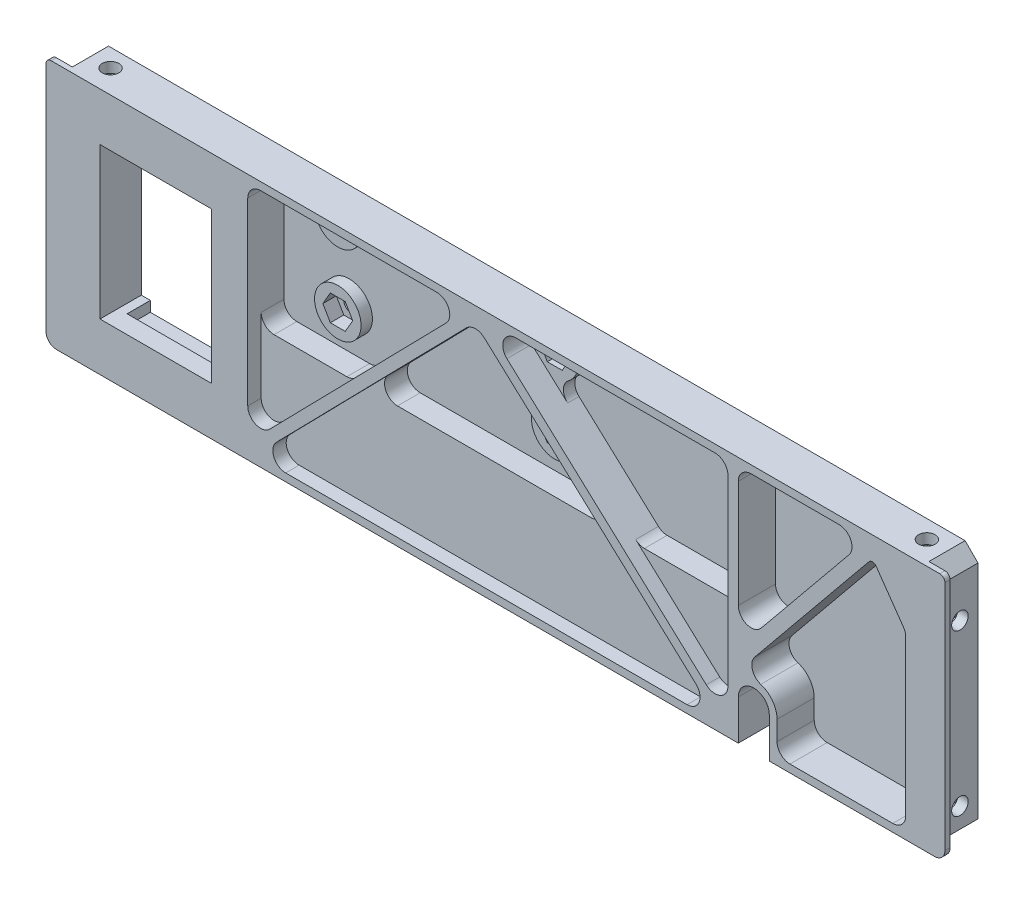
SolidWorks part; units mm, degrees
ref_plane "Front Plane" through (0, 0, 0) normal (0, 0, 1) x (1, 0, 0)
ref_plane "Top Plane" through (0, 0, 0) normal (0, 1, 0) x (1, 0, 0)
ref_plane "Right Plane" through (0, 0, 0) normal (1, 0, 0) x (0, 0, -1)
sketch "Sketch1" plane through (0, 0, 0) normal (0, 0, 1) x (1, 0, 0)
  line L1 (87, -25.55) -> (-87, -25.55)
  line L2 (87, -25.55) -> (87, 25.55)
  line L3 (87, 25.55) -> (-87, 25.55)
  line L4 (-87, -25.55) -> (-87, 25.55)
  line L5 (87, -25.55) -> (-87, 25.55) construction
  line L6 (87, 25.55) -> (-87, -25.55) construction
  point P0 (0, 0)
  dimension "D1" = 174
  dimension "D2" = 51.1
extrude "Boss-Extrude1" add sketch "Sketch1" against normal blind 8
sketch "Sketch2" plane through (0, 0, -8) normal (0, 0, -1) x (-1, 0, 0)
  line L5 (-87, -25.55) -> (-87, 25.55) construction
  line L6 (-87, 25.55) -> (87, 25.55) construction
  line L13 (85.4, -23.95) -> (85.4, 23.95)
  line L14 (-85.4, -23.95) -> (85.4, -23.95)
  line L15 (-85.4, 23.95) -> (-85.4, -23.95)
  line L16 (85.4, 23.95) -> (-85.4, 23.95)
  point P2 (0, 23.95)
  point P5 (85.4, 0)
  dimension "D1" = 1.6
  dimension "D2" = 1.6
extrude "Cut-Extrude1" cut sketch "Sketch2" against normal offset from surface (7 mm away) 1 flip side to cut up to face at (0, 0, 0)
chamfer "Chamfer1" distance 2.5 angle 45 4 edges at (-85.4, -23.95, -4.5) (-85.4, 23.95, -4.5) (85.4, -23.95, -4.5) (85.4, 23.95, -4.5)
fillet "Fillet1" radius 0.5 2 edges at (-87, 25.55, -0.5) (87, 25.55, -0.5)
sketch "Sketch3" plane through (0, 0, 0) normal (0, 0, 1) x (1, 0, 0)
  line L1 (-82.9, 23.95) -> (-85.4, 21.45) construction
  line L2 (-82.9, 23.95) -> (82.9, 23.95) construction
  line L3 (-82.9, 23.95) -> (-85.4, 21.45) construction
  line L4 (-82.9, 23.95) -> (82.9, 23.95) construction
  line L5 (85.4, 21.45) -> (82.9, 23.95) construction
  line L6 (85.4, 21.45) -> (85.4, -21.45) construction
  line L7 (82.9, -23.95) -> (85.4, -21.45) construction
  line L8 (82.9, -23.95) -> (-82.9, -23.95) construction
  line L9 (-85.4, -21.45) -> (-82.9, -23.95) construction
  line L10 (-85.4, -21.45) -> (-85.4, 21.45) construction
  line L11 (85.4, 21.45) -> (82.9, 23.95) construction
  line L12 (85.4, 21.45) -> (85.4, -21.45) construction
  line L13 (82.9, -23.95) -> (85.4, -21.45) construction
  line L14 (82.9, -23.95) -> (-82.9, -23.95) construction
  line L15 (-85.4, -21.45) -> (-82.9, -23.95) construction
  line L16 (-85.4, -21.45) -> (-85.4, 21.45) construction
  line L26 (79.4, -22.45) -> (-79.4, -22.45)
  line L27 (79.4, -22.45) -> (79.4, 22.45)
  line L28 (79.4, 22.45) -> (-79.4, 22.45)
  line L29 (-79.4, -22.45) -> (-79.4, 22.45)
  line L30 (79.4, -22.45) -> (-79.4, 22.45) construction
  line L31 (79.4, 22.45) -> (-79.4, -22.45) construction
  point P4 (0, 0)
  dimension "D1" = 3
  dimension "D2" = 6
extrude "Cut-Extrude2" cut sketch "Sketch3" against normal offset from surface (7.2 mm away) 0.8 up to face at (0, 0, -8)
sketch "Sketch9" plane through (0, 0, 0) normal (0, 0, 1) x (1, 0, 0)
  line L0 (-73.4, 22.45) -> (-73.4, 19.45)
  line L1 (-79.4, 22.45) -> (79.4, 22.45) construction
  line L2 (-73.4, 19.45) -> (-79.4, 10.8811)
  line L3 (-79.4, -22.45) -> (-79.4, 22.45) construction
  line L4 (-79.4, 10.8811) -> (-79.4, 22.45)
  line L5 (-79.4, 22.45) -> (-73.4, 22.45)
  dimension "D1" = 6
  dimension "D2" = 35
  dimension "D3" = 3
extrude "Boss-Extrude2" add sketch "Sketch9" against normal up to surface (7.2 mm away) up to face at (0, 0, -7.2)
hole_wizard "Ø3.0mm Dowel Hole1" positions "Sketch4" profile "Sketch5" hole size "Ø3.0" standard "ANSI Metric"
sketch "Sketch4" plane through (-85.4, 0, 0) normal (-1, 0, 0) x (0, 0, 1)
  line L0 (-4.5, 13.55) -> (-4.5, -17.55) construction
  line L2 (-8, -21.45) -> (-8, 21.45) construction
  line L3 (-1, 25.55) -> (0, 25.55) construction
  line L5 (-1, -25.55) -> (0, -25.55) construction
  point P0 (-4.5, 13.55)
  point P3 (-4.5, -17.55)
  point P15 (-0.5, 25.55)
  dimension "D1" = 3.5
  dimension "D2" = 12
  dimension "D3" = 8
sketch "Sketch5" plane through (-85.4, 13.55, -4.5) normal (0, 1, 0) x (0, 0, 1)
  line L0 (0, 0) -> (0, 5)
  line L1 (0, 5) -> (1.6, 5)
  line L2 (1.6, 5) -> (1.6, 0)
  line L5 (1.6, 0) -> (0, 0)
  line L10 (0, 5) -> (-1.6, 5) construction
  line L11 (0, -6.35) -> (0, 107.95) construction
  dimension "Hole Dia." = 3.2
  dimension "Hole Depth" = 5
  dimension "Drill Angle" = 180
hole_wizard "Ø3.0mm Dowel Hole2" positions "Sketch7" profile "Sketch8" hole size "Ø3.0" standard "ANSI Metric"
sketch "Sketch7" plane through (0, 23.95, 0) normal (0, 1, 0) x (1, 0, 0)
  line L0 (-82.9, 8) -> (82.9, 8) construction
  line L1 (-87, 0) -> (-87, 1) construction
  point P0 (-79, 4.5)
  dimension "D1" = 3.5
  dimension "D2" = 8
sketch "Sketch8" plane through (-79, 23.95, -4.5) normal (1, 0, 0) x (0, 0, 1)
  line L0 (0, 0) -> (0, 5)
  line L1 (0, 5) -> (1.6, 5)
  line L2 (1.6, 5) -> (1.6, 0)
  line L5 (1.6, 0) -> (0, 0)
  line L10 (0, 5) -> (-1.6, 5) construction
  line L11 (0, -6.35) -> (0, 107.95) construction
  dimension "Hole Dia." = 3.2
  dimension "Hole Depth" = 5
  dimension "Drill Angle" = 180
sketch "Sketch10" plane through (-85.4, 0, 0) normal (-1, 0, 0) x (0, 0, 1)
  line L0 (-8, -21.45) -> (-8, 21.45) construction
  line L1 (-8, 16.3) -> (-1.75, 16.3)
  line L2 (-8, 16.3) -> (-8, 10.8)
  line L3 (-8, 10.8) -> (-1.75, 10.8)
  line L4 (-1.75, 16.3) -> (-1.75, 10.8)
  line L6 (-8, -14.8) -> (-1.75, -14.8)
  line L7 (-8, -14.8) -> (-8, -20.3)
  line L8 (-8, -20.3) -> (-1.75, -20.3)
  line L9 (-1.75, -14.8) -> (-1.75, -20.3)
  point P6 (-1.75, -17.55)
  point P8 (-1.75, 13.55)
  dimension "D1" = 5.5
  dimension "D2" = 2.75
extrude "Cut-Extrude3" cut sketch "Sketch10" against normal blind 1.8 from offset 2 offset against normal yes
sketch "Sketch11" plane through (0, 23.95, 0) normal (0, 1, 0) x (1, 0, 0)
  line L0 (-82.9, 8) -> (82.9, 8) construction
  line L1 (-81.75, 8) -> (-76.25, 8)
  line L2 (-81.75, 8) -> (-81.75, 1.75)
  line L3 (-81.75, 1.75) -> (-76.25, 1.75)
  line L4 (-76.25, 8) -> (-76.25, 1.75)
  point P6 (-79, 1.75)
  dimension "D1" = 5.5
  dimension "D2" = 2.75
extrude "Cut-Extrude4" cut sketch "Sketch11" against normal blind 1.8 from offset 2 offset against normal yes
mirror "Mirror1" about plane through (0, 0, 0) normal (1, 0, 0) of "Cut-Extrude4", "Cut-Extrude3", "Ø3.0mm Dowel Hole2", "Ø3.0mm Dowel Hole1", "Boss-Extrude2"
sketch "Sketch12" plane through (0, 0, -7.2) normal (0, 0, 1) x (1, 0, 0)
  line L0 (-73.4, 22.45) -> (-36.7, -22.45) construction
  line L1 (-79.4, -22.45) -> (79.4, -22.45) construction
  line L2 (-36.7, -22.45) -> (0, 22.45) construction
  line L3 (73.4, 22.45) -> (-73.4, 22.45) construction
  line L4 (0, 22.45) -> (36.7, -22.45) construction
  line L5 (36.7, -22.45) -> (73.4, 22.45) construction
  line L6 (-74.3678, 21.6589) -> (-37.4743, -23.4779)
  line L7 (-35.9257, -23.4779) -> (0, 20.4748)
  line L8 (0, 20.4748) -> (35.9257, -23.4779)
  line L9 (37.4743, -23.4779) -> (74.3678, 21.6589)
  line L10 (-72.4322, 23.2411) -> (-36.7, -20.4748)
  line L11 (-36.7, -20.4748) -> (-0.7743, 23.4779)
  line L12 (0.7743, 23.4779) -> (36.7, -20.4748)
  line L13 (36.7, -20.4748) -> (72.4322, 23.2411)
  line L14 (0, 20.4748) -> (36.7, -24.4252) construction
  line L15 (36.7, -24.4252) -> (74.3678, 21.6589) construction
  line L16 (-36.7, -20.4748) -> (0, 24.4252) construction
  line L17 (0, 24.4252) -> (36.7, -20.4748) construction
  line L18 (-74.3678, 21.6589) -> (-36.7, -24.4252) construction
  line L19 (-36.7, -24.4252) -> (0, 20.4748) construction
  arc A0 (-74.3678, 21.6589) -> (-72.4322, 23.2411) centre (-73.4, 22.45) cw
  arc A1 (74.3678, 21.6589) -> (72.4322, 23.2411) centre (73.4, 22.45) ccw
  arc A2 (35.9257, -23.4779) -> (37.4743, -23.4779) centre (36.7, -22.845) ccw
  arc A3 (-0.7743, 23.4779) -> (0.7743, 23.4779) centre (0, 22.845) cw
  arc A4 (-37.4743, -23.4779) -> (-35.9257, -23.4779) centre (-36.7, -22.845) ccw
  dimension "D3" = 1
  dimension "D1" = 1.25
extrude "Boss-Extrude3" add sketch "Sketch12" along normal up to surface (7.2 mm away) up to face at (0, 7.5828, 0)
sketch "Sketch13" plane through (0, 0, 0) normal (0, 0, 1) x (1, 0, 0)
  line L0 (-73.4, 19.45) -> (-73.4, 20.4748)
  line L1 (-73.4, 20.4748) -> (-72.5623, 19.45)
  line L2 (-73.4, 20.4748) -> (-38.3144, -22.45) construction
  line L3 (-72.5623, 19.45) -> (-73.4, 19.45)
  line L4 (0, 0) -> (0, 25.4565) construction
  line L5 (72.5623, 19.45) -> (73.4, 19.45)
  line L6 (73.4, 20.4748) -> (72.5623, 19.45)
  line L7 (73.4, 19.45) -> (73.4, 20.4748)
extrude "Small Fix" add sketch "Sketch13" against normal up to surface (7.2 mm away) up to face at (-68.7829, 1.1812, -7.2)
sketch "Sketch14" plane through (0, 0, -1) normal (0, 0, -1) x (-1, 0, 0)
  line L0 (87, -25.55) -> (87, 25.05) construction
  line L1 (-87, -25.55) -> (87, -25.55)
  line L2 (-87, -25.55) -> (-87, -23.95)
  line L3 (-87, -23.95) -> (87, -23.95)
  line L4 (87, -25.55) -> (87, -23.95)
  line L5 (-82.9, -23.95) -> (82.9, -23.95) construction
extrude "Cut-Extrude5" cut sketch "Sketch14" against normal through all
fillet "Fillet2" radius 2.5 15 edges at (79.4, -22.45, -3.6) (79.4, 10.8811, -3.6) (38.3144, -22.45, -3.6) (71.7856, 22.45, -3.6) (36.7, -20.4748, -3.6) (1.6144, 22.45, -3.6) (35.0856, -22.45, -3.6) (0, 20.4748, -3.6) (-35.0856, -22.45, -3.6) (-1.6144, 22.45, -3.6) (-36.7, -20.4748, -3.6) (-71.7856, 22.45, -3.6) (-79.4, 10.8811, -3.6) (-79.4, -22.45, -3.6) (-38.3144, -22.45, -3.6)
fillet "Fillet3" radius 1 4 edges at (73.4, 19.45, -3.6) (72.5623, 19.45, -3.6) (-72.5623, 19.45, -3.6) (-73.4, 19.45, -3.6)
fillet "Fillet4" radius 2 2 edges at (-87, -23.95, -0.5) (87, -23.95, -0.5)
sketch "Sketch23" plane through (0, 0, -1) normal (0, 0, -1) x (-1, 0, 0)
  line L0 (82.9, 23.95) -> (-82.9, 23.95) construction
  line L1 (-87, 25.55) -> (87, 25.55)
  line L2 (-87, 25.55) -> (-87, 23.95)
  line L3 (-87, 23.95) -> (87, 23.95)
  line L4 (87, 25.55) -> (87, 23.95)
  line L5 (87, -21.95) -> (87, 25.05) construction
  line L6 (86.5, 25.55) -> (-86.5, 25.55) construction
  line L7 (-87, 25.05) -> (-87, -21.95) construction
extrude "Cut-Extrude9" cut sketch "Sketch23" against normal through all
sketch "Sketch24" plane through (0, 0, 0) normal (0, 0, 1) x (1, 0, 0)
  line L0 (79.4, -19.95) -> (79.4, 10.0929) construction
  line L1 (49.95, 22.45) -> (73.6986, 22.45) construction
  line L2 (49.95, 22.45) -> (49.95, -22.45) construction
  line L3 (49.95, -22.45) -> (79.4, -22.45) construction
  line L4 (79.4, 10.0929) -> (79.4, -22.45) construction
  line L5 (43.5867, -22.45) -> (76.9, -22.45) construction
  line L6 (66.5133, 22.45) -> (6.8867, 22.45) construction
  line L7 (78.9479, 11.5268) -> (73.6986, 19.0236) construction
  line L8 (78.9479, 11.5268) -> (73.6986, 19.0236) construction
  line L9 (73.6986, 19.0236) -> (73.6986, 22.45) construction
  line L10 (0, 23.95) -> (0, -23.95) construction
  line L11 (54.95, 14.625) -> (76.55, 14.625) construction
  line L12 (54.95, 14.625) -> (54.95, -14.625) construction
  line L13 (54.95, -14.625) -> (76.55, -14.625) construction
  line L14 (76.55, 14.625) -> (76.55, -14.625) construction
  line L15 (87, 23.95) -> (-87, 23.95) construction
  line L16 (-85, -23.95) -> (85, -23.95) construction
  line L17 (-76.55, 14.625) -> (-76.55, -14.625) construction
  line L18 (-54.95, -14.625) -> (-76.55, -14.625) construction
  line L19 (-54.95, 14.625) -> (-54.95, -14.625) construction
  line L20 (-54.95, 14.625) -> (-76.55, 14.625) construction
  line L21 (-73.6986, 19.0236) -> (-73.6986, 22.45)
  line L22 (-78.9479, 11.5268) -> (-73.6986, 19.0236)
  line L23 (-79.4, 10.0929) -> (-79.4, -22.45)
  line L24 (-49.95, -22.45) -> (-79.4, -22.45)
  line L25 (-49.95, 22.45) -> (-49.95, -22.45)
  line L26 (-49.95, 22.45) -> (-73.6986, 22.45)
  line L27 (87, -21.95) -> (87, 23.95) construction
  arc A0 (79.4, 10.0929) -> (78.9479, 11.5268) centre (76.9, 10.0929) ccw construction
  arc A1 (79.4, 10.0929) -> (78.9479, 11.5268) centre (76.9, 10.0929) ccw construction
  arc A2 (-79.4, 10.0929) -> (-78.9479, 11.5268) centre (-76.9, 10.0929) cw
  point P18 (0, 0)
  point P21 (76.55, 0)
  dimension "D1" = 10.45
  dimension "D2" = 21.6
  dimension "D3" = 29.25
  dimension "D4" = 5
extrude "Boss-Extrude7" add sketch "Sketch24" against normal up to surface (7.2 mm away) up to face at (36.7, 7.6215, -7.2)
sketch "Sketch26" plane through (0, 0, 0) normal (0, 0, 1) x (1, 0, 0)
  line L8 (-54.95, 14.625) -> (-54.95, -14.625) construction
  line L9 (-54.95, -14.625) -> (-76.55, -14.625) construction
  line L10 (-76.55, 14.625) -> (-76.55, -14.625) construction
  line L11 (-54.95, 14.625) -> (-76.55, 14.625) construction
  line L12 (-54.95, 14.625) -> (-54.95, -14.625)
  line L13 (-54.95, -14.625) -> (-76.55, -14.625)
  line L14 (-76.55, 14.625) -> (-76.55, -14.625)
  line L15 (-54.95, 14.625) -> (-76.55, 14.625)
extrude "Cut-Extrude10" cut sketch "Sketch26" against normal up to surface (8 mm away) up to face at (82.5, 13.55, -8)
fillet "Fillet5" radius 1 2 edges at (87, 23.95, -0.5) (-87, 23.95, -0.5)
sketch "Sketch35" plane through (0, 0, -7.2) normal (0, 0, 1) x (1, 0, 0)
  line L0 (47, -16.2) -> (47, -23.95)
  line L4 (-85, -23.95) -> (85, -23.95) construction
  line L5 (53, -16.2) -> (53, -23.95)
  line L6 (53, -23.95) -> (47, -23.95)
  line L7 (50, -23.95) -> (50, -16.2) construction
  line L9 (87, -21.95) -> (87, 22.95) construction
  circle A4 centre (50, -16.2) radius 2.2 construction
  arc A5 (47, -16.2) -> (53, -16.2) centre (50, -16.2) cw
  point P4 (50, -23.95)
  dimension "D2" = 4.4
  dimension "D3" = 6
  dimension "D1" = 7.75
  dimension "D4" = 37
extrude "Cut-Extrude15" cut sketch "Sketch35" against normal through all both and the other way through all
sketch "Sketch37" plane through (0, 0, 0) normal (0, 0, 1) x (1, 0, 0)
  line L6 (47, -16.2) -> (47, -22.45) construction
  line L7 (53, -22.45) -> (53, -16.2) construction
  line L8 (47, -16.2) -> (47, -22.45)
  line L9 (53, -22.45) -> (53, -16.2)
  line L10 (50, -11.7) -> (47.1012, -11.7)
  line L11 (41.6511, -18.3678) -> (72.2622, 19.0829) construction
  line L12 (41.6511, -18.3678) -> (47.1012, -11.7)
  line L13 (54.5, -22.45) -> (54.5, -16.2)
  line L14 (53, -22.45) -> (54.5, -22.45)
  line L16 (47, -22.45) -> (43.5867, -22.45) construction
  line L17 (47, -22.45) -> (43.5867, -22.45)
  line L18 (41.6511, -18.3678) -> (72.2622, 19.0829) construction
  arc A4 (53, -16.2) -> (47, -16.2) centre (50, -16.2) ccw construction
  arc A5 (53, -16.2) -> (47, -16.2) centre (50, -16.2) ccw
  arc A6 (54.5, -16.2) -> (50, -11.7) centre (50, -16.2) ccw
  arc A7 (41.6511, -18.3678) -> (43.5867, -22.45) centre (43.5867, -19.95) ccw construction
  arc A8 (54.5, -16.2) -> (45.5, -16.2) centre (50, -16.2) ccw construction
  arc A9 (41.6511, -18.3678) -> (43.5867, -22.45) centre (43.5867, -19.95) ccw
  dimension "D1" = 1.5
extrude "Boss-Extrude12" add sketch "Sketch37" against normal up to surface (7.2 mm away) up to face at (62.9347, -6.0989, -7.2)
sketch "Sketch38" plane through (0, 0, 0) normal (0, 0, 1) x (1, 0, 0)
  line L1 (47, -23.95) -> (-49.95, -23.95)
  line L2 (47, -23.95) -> (47, 22.45)
  line L3 (47, 22.45) -> (-49.95, 22.45)
  line L4 (-49.95, -23.95) -> (-49.95, 22.45)
extrude "Boss-Extrude13" add sketch "Sketch38" against normal up to surface (8 mm away) up to face at (-65.75, 0, -8)
sketch "Sketch39" plane through (0, 0, -8) normal (0, 0, -1) x (-1, 0, 0)
  line L0 (7.85, -5.15) -> (50.95, -5.15) construction
  line L1 (7.85, -5.15) -> (7.85, -22.45) construction
  line L2 (7.85, -22.45) -> (50.95, -22.45) construction
  line L3 (50.95, -5.15) -> (50.95, -22.45) construction
  line L4 (19.82, 22.45) -> (46.95, 22.45) construction
  line L5 (19.82, 22.45) -> (19.82, 2.45) construction
  line L6 (19.82, 2.45) -> (46.95, 2.45) construction
  line L7 (46.95, 22.45) -> (46.95, 2.45) construction
  line L8 (-35.35, -5.15) -> (-2.65, -5.15) construction
  line L9 (-35.35, -5.15) -> (-35.35, -22.87) construction
  line L10 (-35.35, -22.87) -> (-2.65, -22.87) construction
  line L11 (-2.65, -5.15) -> (-2.65, -22.87) construction
  line L12 (-36.43, 22.35) -> (7.82, 22.35) construction
  line L13 (-36.43, 22.35) -> (-36.43, 2.45) construction
  line L14 (-36.43, 2.45) -> (7.82, 2.45) construction
  line L15 (7.82, 22.35) -> (7.82, 2.45) construction
  line L19 (82.9, 23.95) -> (-82.9, 23.95) construction
  line L20 (-47, -23.95) -> (82.9, -23.95) construction
  line L21 (54.95, 14.625) -> (54.95, -14.625) construction
  dimension "D1" = 43.1
  dimension "D2" = 17.3
  dimension "D3" = 27.13
  dimension "D4" = 20
  dimension "D5" = 32.7
  dimension "D6" = 17.72
  dimension "D7" = 19.9
  dimension "D8" = 44.25
  dimension "D9" = 12
  dimension "D10" = 10.5
  dimension "D11" = 1.5
  dimension "D12" = 1.5
  dimension "D13" = 8
  dimension "D14" = 4
sketch "Sketch40" plane through (0, 0, -8) normal (0, 0, -1) x (-1, 0, 0)
  line L0 (-35.35, -5.15) -> (-35.35, -22.87) construction
  line L1 (-35.35, -22.87) -> (-2.65, -22.87) construction
  line L2 (-2.65, -5.15) -> (-2.65, -22.87) construction
  line L3 (-35.35, -5.15) -> (-2.65, -5.15) construction
  line L4 (-35.35, -5.15) -> (-35.35, -22.87) construction
  line L5 (-35.35, -22.87) -> (-2.65, -22.87) construction
  line L6 (-2.65, -5.15) -> (-2.65, -22.87) construction
  line L7 (-35.35, -5.15) -> (-2.65, -5.15) construction
  line L8 (7.85, -5.15) -> (7.85, -22.45) construction
  line L9 (7.85, -22.45) -> (50.95, -22.45) construction
  line L10 (50.95, -5.15) -> (50.95, -22.45) construction
  line L11 (7.85, -5.15) -> (50.95, -5.15) construction
  line L12 (7.85, -5.15) -> (7.85, -22.45) construction
  line L13 (7.85, -22.45) -> (50.95, -22.45) construction
  line L14 (50.95, -5.15) -> (50.95, -22.45) construction
  line L15 (7.85, -5.15) -> (50.95, -5.15) construction
  line L16 (-35.5, -5) -> (-35.5, -23.02)
  line L17 (-35.5, -23.02) -> (-2.5, -23.02)
  line L18 (-2.5, -5) -> (-2.5, -23.02)
  line L19 (-35.5, -5) -> (-2.5, -5)
  line L20 (7.7, -5) -> (7.7, -22.6)
  line L21 (7.7, -22.6) -> (51.1, -22.6)
  line L22 (51.1, -5) -> (51.1, -22.6)
  line L23 (7.7, -5) -> (51.1, -5)
  dimension "D1" = 0.15
extrude "Cut-Extrude16" cut sketch "Sketch40" against normal blind 2
sketch "Sketch42" plane through (0, 0, -6) normal (0, 0, -1) x (-1, 0, 0)
  line L0 (51.1, -5) -> (7.7, -5) construction
  line L1 (7.7, -5) -> (14.7, -5)
  line L2 (7.7, -5) -> (7.7, -22.6)
  line L3 (7.7, -22.6) -> (14.7, -22.6)
  line L4 (14.7, -5) -> (14.7, -22.6)
  line L5 (7.7, -22.6) -> (51.1, -22.6) construction
  line L6 (7.7, -22.6) -> (51.1, -22.6) construction
  line L7 (48.1, -5) -> (19.7, -5)
  line L8 (48.1, -5) -> (48.1, -22.6)
  line L9 (48.1, -22.6) -> (19.7, -22.6)
  line L10 (19.7, -5) -> (19.7, -22.6)
  line L13 (51.1, -22.6) -> (51.1, -5) construction
  dimension "D1" = 3
  dimension "D2" = 7
  dimension "D3" = 5
extrude "Cut-Extrude17" cut sketch "Sketch42" against normal blind 2.4
sketch "Sketch43" plane through (0, 0, 0) normal (0, 0, 1) x (1, 0, 0)
  line L0 (47, -7.8735) -> (47, 22.45) construction
  line L1 (45, 22.45) -> (-47.95, 22.45)
  line L2 (45, 22.45) -> (45, -22.45)
  line L3 (45, -22.45) -> (-47.95, -22.45)
  line L4 (-47.95, 22.45) -> (-47.95, -22.45)
  line L5 (66.5133, 22.45) -> (47, 22.45) construction
  line L8 (-54.95, -14.625) -> (-54.95, 14.625) construction
  point P8 (45, 0)
  dimension "D1" = 2
  dimension "D2" = 7
extrude "Cut-Extrude18" cut sketch "Sketch43" against normal offset from surface (2.6 mm away) 1 up to face at (-33.9, -13.8, -3.6)
sketch "Sketch44" plane through (0, 0, -2.6) normal (0, 0, 1) x (1, 0, 0)
  line L0 (-47.95, 22.45) -> (-47.95, -22.45) construction
  line L1 (-47.95, -3) -> (45, -3)
  line L2 (-47.95, -3) -> (-47.95, 22.45)
  line L3 (-47.95, 22.45) -> (45, 22.45)
  line L4 (45, -3) -> (45, 22.45)
  line L5 (2.5, -5) -> (35.5, -5) construction
  dimension "D1" = 2
extrude "Cut-Extrude19" cut sketch "Sketch44" against normal offset from surface (4.4 mm away) 1 up to face at (19, -14.01, -8)
sketch "Sketch45" plane through (0, 0, -8) normal (0, 0, -1) x (-1, 0, 0)
  circle A0 centre (-6.68, 19.2) radius 1.45
  circle A1 centre (-6.68, 5.6) radius 1.45
  circle A2 centre (35.32, 20.16) radius 1.45
  circle A3 centre (35.32, 4.74) radius 1.45
  dimension "D1" = 2.9
extrude "Cut-Extrude20" cut sketch "Sketch45" against normal through all
sketch "Sketch46" plane through (0, 0, -7) normal (0, 0, 1) x (1, 0, 0)
  line L0 (-35.32, 23.95) -> (-35.32, 20.16) construction
  line L1 (-36.7634, 17.66) -> (-33.8766, 17.66) construction
  line L2 (-33.8766, 17.66) -> (-32.4332, 20.16) construction
  line L3 (-32.4332, 20.16) -> (-33.8766, 22.66) construction
  line L4 (-33.8766, 22.66) -> (-36.7634, 22.66) construction
  line L5 (-36.7634, 22.66) -> (-38.2068, 20.16) construction
  line L6 (-38.2068, 20.16) -> (-36.7634, 17.66) construction
  line L7 (5.2366, 16.7) -> (8.1234, 16.7) construction
  line L8 (8.1234, 16.7) -> (9.5668, 19.2) construction
  line L9 (9.5668, 19.2) -> (8.1234, 21.7) construction
  line L10 (8.1234, 21.7) -> (5.2366, 21.7) construction
  line L11 (5.2366, 21.7) -> (3.7932, 19.2) construction
  line L12 (3.7932, 19.2) -> (5.2366, 16.7) construction
  line L13 (3.7932, 5.6) -> (5.2366, 3.1) construction
  line L14 (5.2366, 3.1) -> (8.1234, 3.1) construction
  line L15 (8.1234, 3.1) -> (9.5668, 5.6) construction
  line L16 (9.5668, 5.6) -> (8.1234, 8.1) construction
  line L17 (8.1234, 8.1) -> (5.2366, 8.1) construction
  line L18 (5.2366, 8.1) -> (3.7932, 5.6) construction
  line L19 (-33.8766, 7.24) -> (-36.7634, 7.24) construction
  line L20 (-36.7634, 7.24) -> (-38.2068, 4.74) construction
  line L21 (-38.2068, 4.74) -> (-36.7634, 2.24) construction
  line L22 (-36.7634, 2.24) -> (-33.8766, 2.24) construction
  line L23 (-33.8766, 2.24) -> (-32.4332, 4.74) construction
  line L24 (-32.4332, 4.74) -> (-33.8766, 7.24) construction
  line L25 (-30.82, 23.95) -> (-30.82, 20.16)
  line L26 (-39.82, 23.95) -> (-39.82, 20.16)
  line L27 (86, 23.95) -> (-86, 23.95) construction
  line L28 (-39.82, 23.95) -> (-30.82, 23.95)
  line L30 (2.18, 23.95) -> (11.18, 23.95)
  line L31 (2.18, 23.95) -> (2.18, 19.2)
  line L32 (2.18, 19.2) -> (11.18, 19.2) construction
  line L33 (11.18, 23.95) -> (11.18, 19.2)
  circle A0 centre (-35.32, 20.16) radius 2.5 construction
  circle A1 centre (6.68, 19.2) radius 2.5 construction
  circle A2 centre (6.68, 5.6) radius 2.5 construction
  circle A3 centre (-35.32, 4.74) radius 2.5 construction
  arc A5 (-39.82, 20.16) -> (-30.82, 20.16) centre (-35.32, 20.16) ccw
  circle A6 centre (-35.32, 4.74) radius 4.5
  circle A7 centre (6.68, 5.6) radius 4.5
  arc A8 (2.18, 19.2) -> (11.18, 19.2) centre (6.68, 19.2) ccw
  circle A9 centre (6.68, 5.6) radius 1.45 construction
  circle A10 centre (6.68, 19.2) radius 1.45 construction
  circle A11 centre (-35.32, 4.74) radius 1.45 construction
  circle A12 centre (-35.32, 20.16) radius 1.45 construction
  circle A13 centre (6.68, 5.6) radius 1.45
  circle A14 centre (6.68, 19.2) radius 1.45
  circle A15 centre (-35.32, 4.74) radius 1.45
  circle A16 centre (-35.32, 20.16) radius 1.45
  point P38 (-35.32, 20.16)
  dimension "D2" = 4.5
  dimension "D1" = 5
extrude "Boss-Extrude14" add sketch "Sketch46" along normal blind 2.2
sketch "Sketch47" plane through (0, 0, -4.8) normal (0, 0, 1) x (1, 0, 0)
  line L0 (-32.4332, 20.16) -> (-33.8766, 22.66) construction
  line L1 (-33.8766, 17.66) -> (-32.4332, 20.16) construction
  line L2 (-36.7634, 17.66) -> (-33.8766, 17.66) construction
  line L3 (-38.2068, 20.16) -> (-36.7634, 17.66) construction
  line L4 (-36.7634, 22.66) -> (-38.2068, 20.16) construction
  line L5 (-33.8766, 22.66) -> (-36.7634, 22.66) construction
  line L6 (-32.4332, 20.16) -> (-33.8766, 22.66)
  line L7 (-33.8766, 17.66) -> (-32.4332, 20.16)
  line L8 (-36.7634, 17.66) -> (-33.8766, 17.66)
  line L9 (-38.2068, 20.16) -> (-36.7634, 17.66)
  line L10 (-36.7634, 22.66) -> (-38.2068, 20.16)
  line L11 (-33.8766, 22.66) -> (-36.7634, 22.66)
  line L12 (-32.4332, 4.74) -> (-33.8766, 7.24) construction
  line L13 (-33.8766, 2.24) -> (-32.4332, 4.74) construction
  line L14 (-36.7634, 2.24) -> (-33.8766, 2.24) construction
  line L15 (-38.2068, 4.74) -> (-36.7634, 2.24) construction
  line L16 (-36.7634, 7.24) -> (-38.2068, 4.74) construction
  line L17 (-33.8766, 7.24) -> (-36.7634, 7.24) construction
  line L18 (-32.4332, 4.74) -> (-33.8766, 7.24)
  line L19 (-33.8766, 2.24) -> (-32.4332, 4.74)
  line L20 (-36.7634, 2.24) -> (-33.8766, 2.24)
  line L21 (-38.2068, 4.74) -> (-36.7634, 2.24)
  line L22 (-36.7634, 7.24) -> (-38.2068, 4.74)
  line L23 (-33.8766, 7.24) -> (-36.7634, 7.24)
  line L24 (9.5668, 5.6) -> (8.1234, 8.1) construction
  line L25 (8.1234, 3.1) -> (9.5668, 5.6) construction
  line L26 (5.2366, 3.1) -> (8.1234, 3.1) construction
  line L27 (3.7932, 5.6) -> (5.2366, 3.1) construction
  line L28 (5.2366, 8.1) -> (3.7932, 5.6) construction
  line L29 (8.1234, 8.1) -> (5.2366, 8.1) construction
  line L30 (9.5668, 5.6) -> (8.1234, 8.1)
  line L31 (8.1234, 3.1) -> (9.5668, 5.6)
  line L32 (5.2366, 3.1) -> (8.1234, 3.1)
  line L33 (3.7932, 5.6) -> (5.2366, 3.1)
  line L34 (5.2366, 8.1) -> (3.7932, 5.6)
  line L35 (8.1234, 8.1) -> (5.2366, 8.1)
  line L36 (3.7932, 19.2) -> (5.2366, 16.7) construction
  line L37 (5.2366, 21.7) -> (3.7932, 19.2) construction
  line L38 (8.1234, 21.7) -> (5.2366, 21.7) construction
  line L39 (9.5668, 19.2) -> (8.1234, 21.7) construction
  line L40 (8.1234, 16.7) -> (9.5668, 19.2) construction
  line L41 (5.2366, 16.7) -> (8.1234, 16.7) construction
  line L42 (3.7932, 19.2) -> (5.2366, 16.7)
  line L43 (5.2366, 21.7) -> (3.7932, 19.2)
  line L44 (8.1234, 21.7) -> (5.2366, 21.7)
  line L45 (9.5668, 19.2) -> (8.1234, 21.7)
  line L46 (8.1234, 16.7) -> (9.5668, 19.2)
  line L47 (5.2366, 16.7) -> (8.1234, 16.7)
extrude "Cut-Extrude21" cut sketch "Sketch47" against normal offset from surface (2.6 mm away) 0.6 up to face at (5.23, 5.6, -8)
sketch "Sketch48" plane through (0, 0, 0) normal (0, 0, 1) x (1, 0, 0)
  line L0 (-47.95, -22.45) -> (-4, 22.45) construction
  line L1 (45, 22.45) -> (-47.95, 22.45) construction
  line L2 (-4, 22.45) -> (45, -22.45) construction
  line L4 (-47.2354, -23.1495) -> (-3.9622, 21.059)
  line L5 (-3.9622, 21.059) -> (44.3244, -23.1873)
  line L6 (-48.6646, -21.7505) -> (-4.0378, 23.841)
  line L7 (-4.0378, 23.841) -> (45.6756, -21.7127)
  line L8 (-47.2354, -23.1495) -> (-48.6646, -21.7505)
  line L9 (44.3244, -23.1873) -> (45.6756, -21.7127)
  dimension "D1" = 1
  dimension "D3" = 4
  dimension "D2" = 1
extrude "Boss-Extrude15" add sketch "Sketch48" against normal up to next
sketch "Sketch49" plane through (0, 0, -4.8) normal (0, 0, 1) x (1, 0, 0)
  line L0 (-2.5198, 22.45) -> (2.18, 22.45) construction
  line L1 (2.18, 22.45) -> (2.18, 19.2) construction
  line L2 (45, -21.0937) -> (-2.5198, 22.45) construction
  line L3 (-2.5198, 22.45) -> (2.18, 22.45)
  line L4 (2.18, 22.45) -> (2.18, 19.2)
  line L5 (2.3451, 17.9921) -> (-2.5198, 22.45)
  arc A0 (2.18, 19.2) -> (2.3451, 17.9921) centre (6.68, 19.2) ccw construction
  arc A1 (2.18, 19.2) -> (2.3451, 17.9921) centre (6.68, 19.2) ccw
extrude "Boss-Extrude16" add sketch "Sketch49" against normal up to surface (2.2 mm away) up to face at (24.0845, 11.9378, -7)
fillet "Fillet6" radius 2.5 24 edges at (47, 22.45, -3.6) (47, -7.8735, -3.6) (47.1012, -11.7, -3.6) (54.5, -22.45, -3.6) (-47.95, -21.0204, -1.3) (-46.5507, -22.45, -1.3) (43.5198, -22.45, -1.3) (45, -21.0937, -1.3) (45, 22.45, -3.5) (25.2541, -3, -4.8) (45, -3, -4.8) (22.2938, -3, -4.8) (-27.5122, -3, -4.8) (-47.95, -3, -4.8) (-30.3109, -3, -4.8) (-39.82, 22.45, -5.9) (-30.82, 22.45, -5.9) (-47.95, 22.45, -3.5) (-5.3993, 22.45, -3.5) (-3.9622, 21.059, -3.5) (5.8545, 14.7764, -5.9) (-2.5198, 22.45, -2.4) (8.3469, 9.7799, -5.9) (10.6987, 7.6248, -5.9)
sketch "Sketch50" plane through (0, 0, -8) normal (0, 0, -1) x (-1, 0, 0)
  line L0 (76.55, 14.625) -> (54.95, 14.625) construction
  line L1 (74.8, 14.625) -> (56.7, 14.625)
  line L2 (74.8, 14.625) -> (74.8, 16.625)
  line L3 (74.8, 16.625) -> (56.7, 16.625)
  line L4 (56.7, 14.625) -> (56.7, 16.625)
  line L10 (54.95, 0) -> (76.55, 0) construction
  line L11 (54.95, 14.625) -> (54.95, -14.625) construction
  line L12 (76.55, -14.625) -> (76.55, 14.625) construction
  line L13 (56.7, -14.625) -> (56.7, -16.625)
  line L14 (74.8, -16.625) -> (56.7, -16.625)
  line L15 (74.8, -14.625) -> (74.8, -16.625)
  line L16 (74.8, -14.625) -> (56.7, -14.625)
  point P16 (65.75, 14.625)
  point P17 (65.75, 14.625)
  dimension "D1" = 2
  dimension "D2" = 1.75
extrude "Cut-Extrude22" cut sketch "Sketch50" against normal offset from surface (4.5 mm away) 3.5 up to face at (29.8456, 8.3364, 0)
sketch "Sketch51" plane through (0, 0, 0) normal (0, 0, 1) x (1, 0, 0)
  line L1 (-85.4, 23.95) -> (-51.1, 23.95)
  line L2 (-85.4, 23.95) -> (-85.4, -23.95)
  line L3 (-85.4, -23.95) -> (-51.1, -23.95)
  line L4 (-51.1, 23.95) -> (-51.1, -23.95)
  line L5 (-82.9, 23.95) -> (82.9, 23.95) construction
  line L6 (47, -23.95) -> (-82.9, -23.95) construction
  line L7 (-51.1, -22.6) -> (-51.1, -5) construction
  line L8 (-85.4, -21.45) -> (-85.4, 21.45) construction
extrude "Cut-Extrude23" [suppressed] cut sketch "Sketch51" against normal through all flip side to cut
